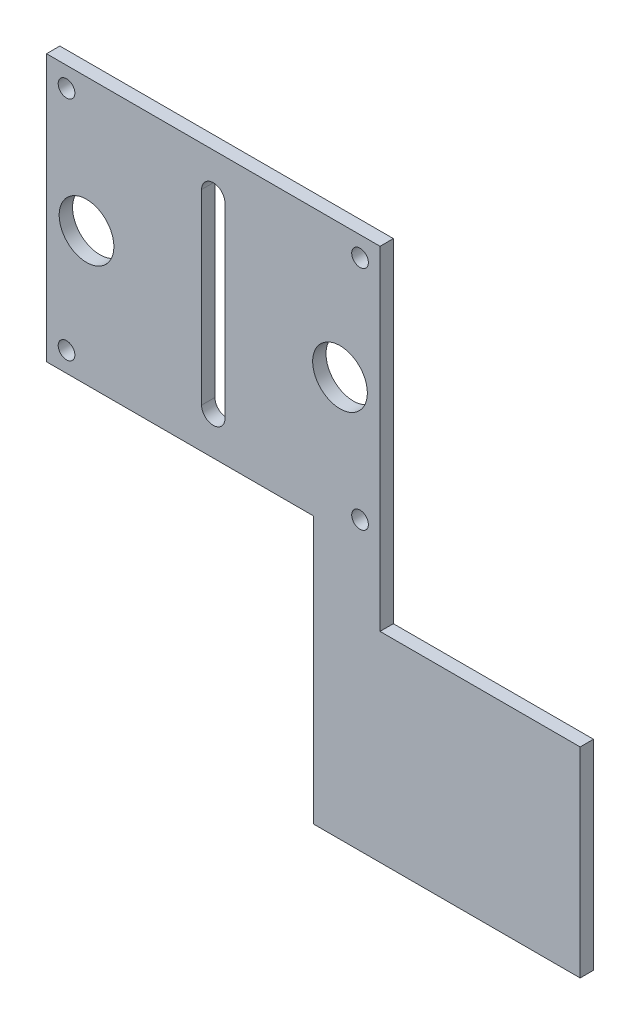
SolidWorks part; units mm, degrees
ref_plane "Front Plane" through (0, 0, 0) normal (0, 0, 1) x (1, 0, 0)
ref_plane "Top Plane" through (0, 0, 0) normal (0, 1, 0) x (1, 0, 0)
ref_plane "Right Plane" through (0, 0, 0) normal (1, 0, 0) x (0, 0, -1)
sketch "Sketch1" plane through (0, 0, 0) normal (0, 0, 1) x (1, 0, 0)
  line L1 (0, 0) -> (50, 0)
  line L2 (0, 0) -> (0, 40)
  line L3 (0, 40) -> (50, 40)
  line L4 (50, 0) -> (50, 40)
  line L5 (40, 0) -> (80, 0)
  line L6 (40, 0) -> (40, -40)
  line L7 (40, -40) -> (80, -40)
  line L8 (80, 0) -> (80, -40)
  line L9 (50, 0) -> (80, 0)
  line L10 (50, 0) -> (50, -10)
  line L11 (50, -10) -> (80, -10)
  line L12 (80, 0) -> (80, -10)
  dimension "D1" = 50
  dimension "D2" = 40
  dimension "D3" = 40
  dimension "D4" = 40
  dimension "D5" = 10
  dimension "D6" = 10
extrude "plate_body" add sketch "Sketch1" along normal blind 2 contours L1 L4 L3 L2 | L8 L5 L1 L6 L7 region at (25, 20, 0) region at (58.8462, -23.4615, 0)
sketch "Sketch2" plane through (0, 0, 2) normal (0, 0, 1) x (1, 0, 0)
  line L2 (0, 0) -> (0, 40) construction
  line L3 (0, 40) -> (50, 40) construction
  circle A0 centre (6, 20) radius 4.1
  circle A1 centre (44, 20) radius 4.1
  dimension "D1" = 38
  dimension "D2" = 8.2
  dimension "D3" = 8.2
  dimension "D4" = 6
  dimension "D5" = 20
  dimension "D6" = 20
extrude "shaft_bearings" cut sketch "Sketch2" against normal through all
sketch "Sketch4" plane through (0, 0, 2) normal (0, 0, 1) x (1, 0, 0)
  line L0 (25, 34) -> (25, 6) construction
  line L1 (26.75, 34) -> (26.75, 6)
  line L2 (23.25, 34) -> (23.25, 6)
  line L5 (0, 0) -> (0, 40) construction
  line L6 (0, 0) -> (40, 0) construction
  arc A0 (26.75, 34) -> (23.25, 34) centre (25, 34) ccw
  arc A1 (23.25, 6) -> (26.75, 6) centre (25, 6) ccw
  point P2 (25, 20)
  dimension "D4" = 6
  dimension "D1" = 3.5
  dimension "D2" = 28
  dimension "D3" = 25
extrude "slot" cut sketch "Sketch4" against normal through all
sketch "Sketch5" plane through (0, 0, 2) normal (0, 0, 1) x (1, 0, 0)
  line L0 (0, 40) -> (50, 40) construction
  line L1 (0, 0) -> (0, 40) construction
  line L2 (0, 0) -> (40, 0) construction
  line L3 (50, -10) -> (50, 40) construction
  circle A0 centre (3, 37) radius 1.25
  circle A1 centre (47, 37) radius 1.25
  circle A2 centre (3, 3) radius 1.25
  circle A3 centre (47, 3) radius 1.25
  dimension "D1" = 2.5
  dimension "D2" = 2.5
  dimension "D3" = 2.5
  dimension "D4" = 2.5
  dimension "D5" = 3
  dimension "D6" = 3
  dimension "D7" = 3
  dimension "D8" = 3
  dimension "D9" = 3
  dimension "D10" = 3
  dimension "D11" = 3
  dimension "D12" = 3
extrude "bolt_holes" cut sketch "Sketch5" against normal through all
